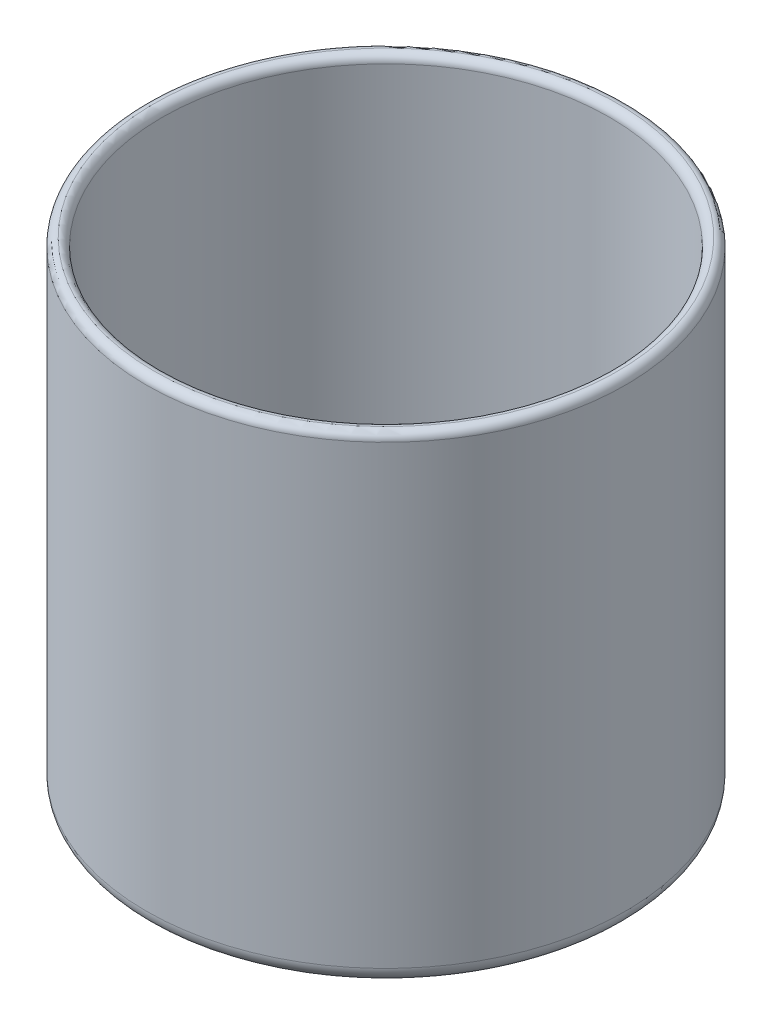
SolidWorks part; units mm, degrees
ref_plane "Спереди" through (0, 0, 0) normal (0, 0, 1) x (1, 0, 0)
ref_plane "Сверху" through (0, 0, 0) normal (0, 1, 0) x (1, 0, 0)
ref_plane "Справа" through (0, 0, 0) normal (1, 0, 0) x (0, 0, -1)
other "Configuration Table"
sketch "Эскиз1" plane through (0, 0, 0) normal (0, 1, 0) x (1, 0, 0)
  circle A0 centre (0, 0) radius 30
  point P3 (-234.8204, 30.7301)
extrude "Бобышка-Вытянуть1" add sketch "Эскиз1" along normal blind 60
sketch "Эскиз2" plane through (0, 60, 0) normal (0, 1, 0) x (1, 0, 0)
  line L0 (0, -30) -> (0, 30) construction
  line L1 (29.4714, 0) -> (-30.7288, 0) construction
  circle A0 centre (0, 0) radius 30 construction
  circle A1 centre (0, 0) radius 28
  point P7 (0, 0)
  point P11 (-0.6287, 0)
extrude "Вырез-Вытянуть1" cut sketch "Эскиз2" against normal blind 55
sketch "Эскиз3" plane through (0, 0, 0) normal (0, -1, 0) x (1, 0, 0)
  line L0 (0, -30) -> (0, 30) construction
  line L1 (-30, 0) -> (30, 0) construction
  circle A0 centre (0, 0) radius 30 construction
  circle A1 centre (0, 10) radius 1.5
  circle A2 centre (0, -10) radius 1.5
  circle A3 centre (10, 0) radius 1.5
  circle A4 centre (-10, 0) radius 1.5
  dimension "D5" = 3
  dimension "D6" = 3
  dimension "D7" = 3
  dimension "D8" = 3
  dimension "D1" = 20
  dimension "D2" = 20
  dimension "D3" = 20
  dimension "D4" = 20
extrude "Вырез-Вытянуть2" cut sketch "Эскиз3" against normal blind 5
fillet "Скругление1" radius 2 1 edges at (0, 0, 30)
fillet "Скругление2" radius 2 1 edges at (0, 5, 28)
fillet "Скругление3" radius 2 4 edges at (-10, 5, -1.5) (0, 5, 8.5) (0, 5, -11.5) (10, 5, -1.5)
fillet "Скругление4" radius 1 4 edges at (0, 0, 8.5) (-10, 0, -1.5) (0, 0, -11.5) (10, 0, -1.5)
fillet "Скругление5" radius 1 1 edges at (0, 60, 30)
fillet "Скругление6" radius 1 1 edges at (0, 60, 28)
